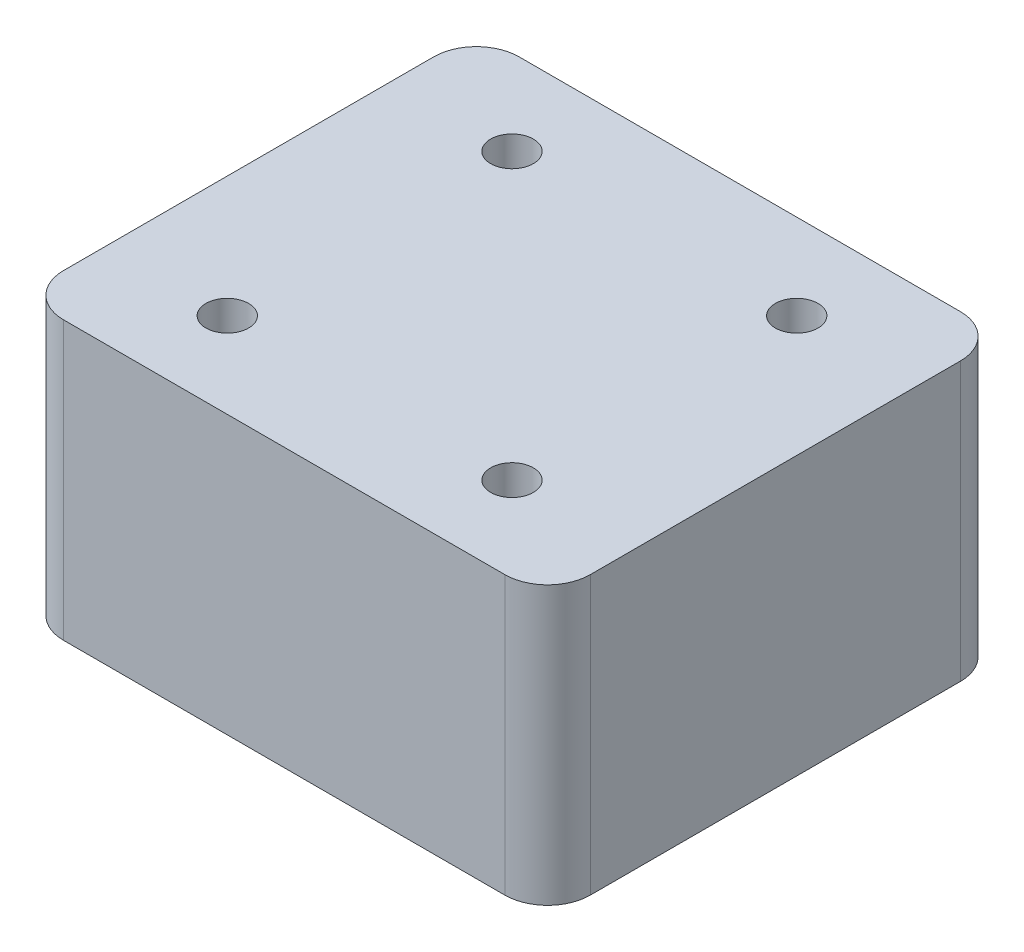
SolidWorks part; units mm, degrees
ref_plane "Front Plane" through (0, 0, 0) normal (0, 0, 1) x (1, 0, 0)
ref_plane "Top Plane" through (0, 0, 0) normal (0, 1, 0) x (1, 0, 0)
ref_plane "Right Plane" through (0, 0, 0) normal (1, 0, 0) x (0, 0, -1)
sketch "Sketch1" plane through (0, 0, 0) normal (0, 1, 0) x (1, 0, 0)
  line L1 (-10, -10) -> (10, -10) construction
  line L2 (-10, -10) -> (-10, 10) construction
  line L3 (-10, 10) -> (10, 10) construction
  line L4 (10, -10) -> (10, 10) construction
  line L5 (-10, -10) -> (10, 10) construction
  line L6 (-10, 10) -> (10, -10) construction
  line L7 (-18.5, -16) -> (18.5, -16)
  line L8 (-18.5, -16) -> (-18.5, 16)
  line L9 (-18.5, 16) -> (18.5, 16)
  line L10 (18.5, -16) -> (18.5, 16)
  line L11 (-18.5, -16) -> (18.5, 16) construction
  line L12 (-18.5, 16) -> (18.5, -16) construction
  circle A0 centre (-10, 10) radius 1.5
  circle A1 centre (10, 10) radius 1.5
  circle A2 centre (10, -10) radius 1.5
  circle A3 centre (-10, -10) radius 1.5
  point P0 (0, 0)
  point P10 (0, 0)
  dimension "D2" = 3
  dimension "D1" = 20
  dimension "D3" = 37
  dimension "D4" = 32
extrude "Boss-Extrude1" add sketch "Sketch1" against normal blind 19.5 contours L10 L9 L8 L7
extrude "Cut-Extrude1" cut sketch "Sketch1<3>" against normal blind 10 contours A3 | A0 | A1 | A2
sketch "Sketch1<3>" plane through (0, 0, 0) normal (0, 1, 0) x (1, 0, 0) same geometry as "Sketch1"
fillet "Fillet1" radius 3 4 edges at (-18.5, -9.75, -16) (18.5, -9.75, -16) (18.5, -9.75, 16) (-18.5, -9.75, 16)
